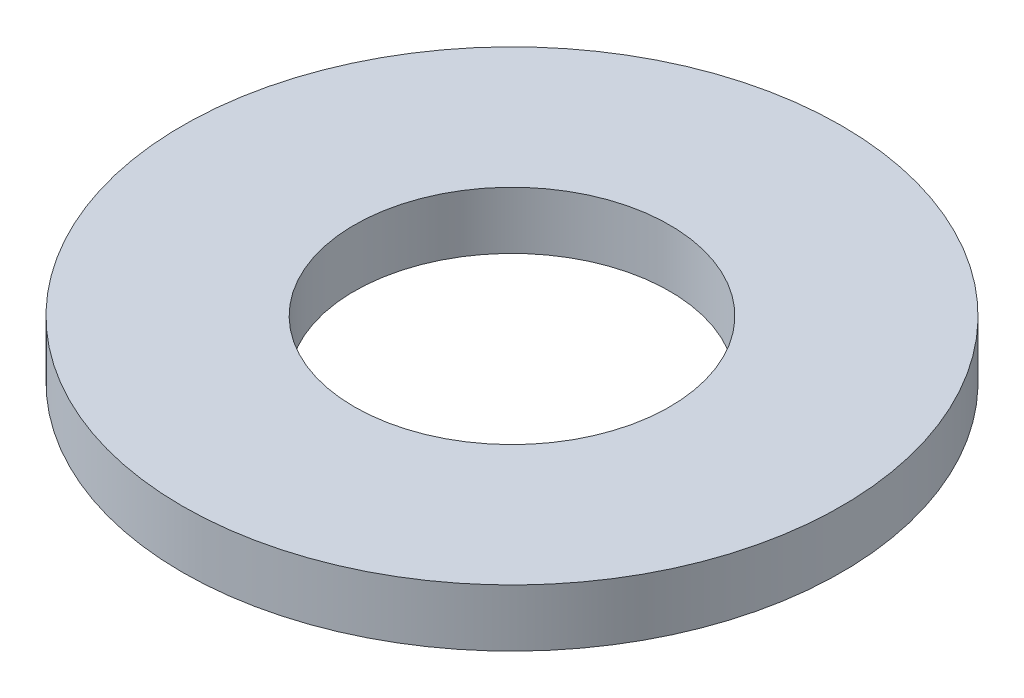
SolidWorks part; units mm, degrees
ref_plane "Front Plane" through (0, 0, 0) normal (0, 0, 1) x (1, 0, 0)
ref_plane "Top Plane" through (0, 0, 0) normal (0, 1, 0) x (1, 0, 0)
ref_plane "Right Plane" through (0, 0, 0) normal (1, 0, 0) x (0, 0, -1)
sketch "Sketch1" plane through (0, 0, 0) normal (0, 1, 0) x (1, 0, 0)
  circle A0 centre (0, 0) radius 57.5
  dimension "FLANGE_OD" = 115
extrude "Boss-Extrude1" add sketch "Sketch1" along normal blind 10
sketch "Sketch2" plane through (0, 0, 0) normal (0, 1, 0) x (1, 0, 0)
  circle A0 centre (0, 0) radius 27.5
  dimension "BORE_D" = 55
extrude "Cut-Extrude1" cut sketch "Sketch2" along normal through all
sketch "Sketch3" plane through (0, 10, 0) normal (0, 1, 0) x (1, 0, 0)
  circle A0 centre (0, 0) radius 16.9216 construction
  circle A1 centre (-16.9216, 0) radius 3.6833
  dimension "BOLT_D" = 7.3666
  dimension "BOLT_PCD" = 33.8433
extrude "Cut-Extrude2" cut sketch "Sketch3" against normal blind 8.9128 rebuild error yes
pattern_circular "CirPattern1" count 6 over 360 rebuild error yes
